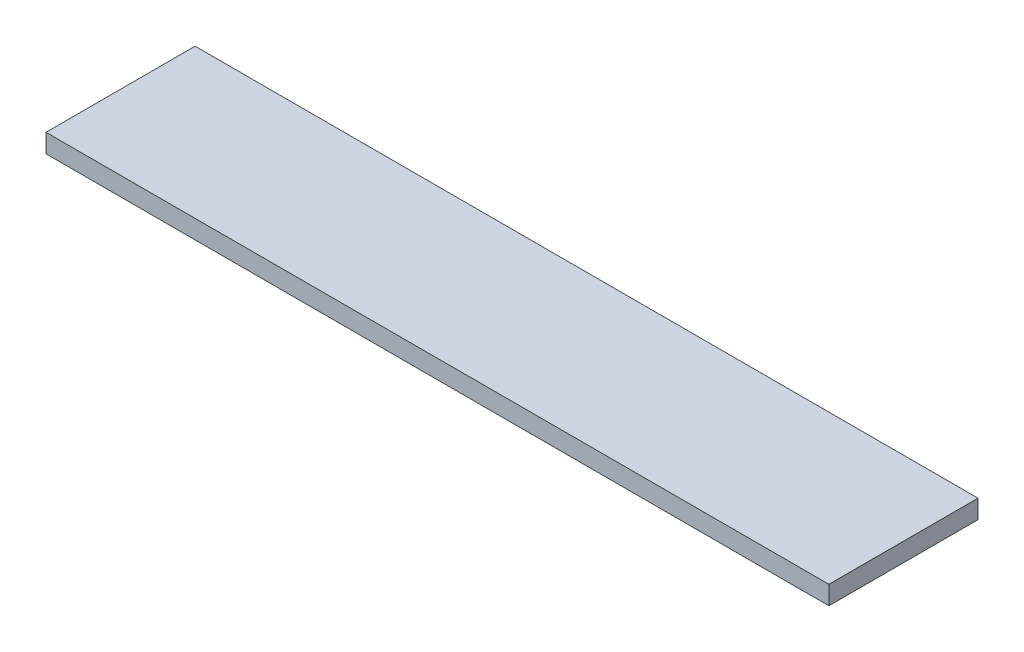
SolidWorks part; units mm, degrees
material "6061-T6 (SS)"
ref_plane "Front" through (0, 0, 0) normal (0, 0, 1) x (1, 0, 0)
ref_plane "Top" through (0, 0, 0) normal (0, 1, 0) x (1, 0, 0)
ref_plane "Right" through (0, 0, 0) normal (1, 0, 0) x (0, 0, -1)
sketch "Sketch1" plane through (0, 0, 0) normal (0, 1, 0) x (1, 0, 0)
  line L0 (266.7, 0) -> (266.7, 50.8) construction
  line L1 (0, 0) -> (266.7, 0)
  line L2 (0, 0) -> (0, 50.8)
  line L3 (0, 50.8) -> (266.7, 50.8)
  line L4 (266.7, 0) -> (266.7, 50.8)
  dimension "D1" = 50.8
extrude "Boss-Extrude1" add sketch "Sketch1" along normal blind 6.35
